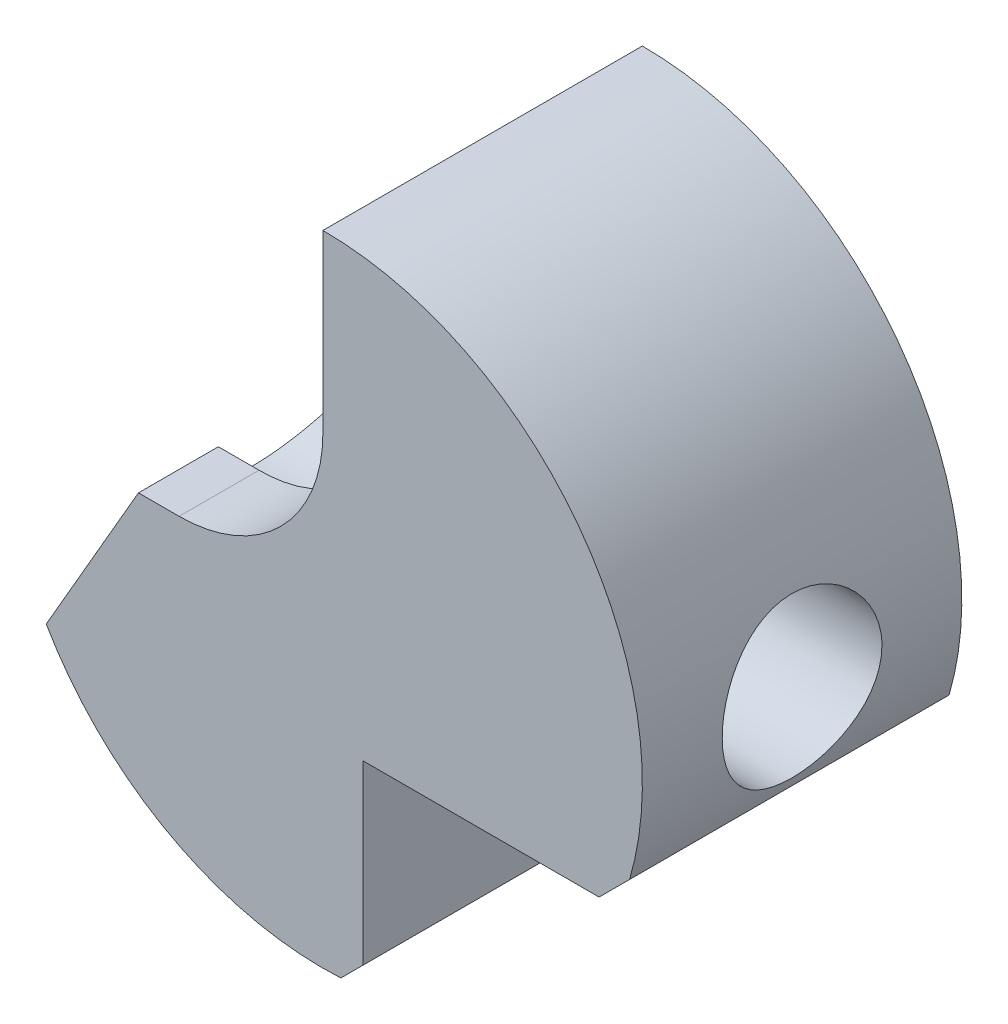
SolidWorks part; units mm, degrees
ref_plane "Front Plane" through (0, 0, 0) normal (0, 0, 1) x (1, 0, 0)
ref_plane "Top Plane" through (0, 0, 0) normal (0, 1, 0) x (1, 0, 0)
ref_plane "Right Plane" through (0, 0, 0) normal (1, 0, 0) x (0, 0, -1)
sketch "Sketch1" plane through (0, 0, 0) normal (0, 0, 1) x (1, 0, 0)
  circle A0 centre (0, 0) radius 20
  dimension "D1" = 40
extrude "Boss-Extrude1" add sketch "Sketch1" along normal mid plane 20
sketch "Sketch2" plane through (0, 0, 10) normal (0, 0, 1) x (1, 0, 0)
  line L0 (0, 20) -> (0, 24.3366)
  line L1 (0, 24.3366) -> (-29.8594, 24.3366)
  line L2 (-29.8594, 24.3366) -> (-29.8594, -31.718)
  line L3 (-29.8594, -31.718) -> (0, 20)
  circle A0 centre (0, 0) radius 20 construction
  dimension "D1" = 150
extrude "Cut-Extrude1" cut sketch "Sketch2" against normal mid plane 66
sketch "Sketch4" plane through (0, 0, 0) normal (1, 0, 0) x (0, 0, -1)
  line L1 (0, 0) -> (-24.3942, 0)
  line L2 (0, 0) -> (0, 23.6702)
  line L3 (0, 23.6702) -> (-24.3942, 23.6702)
  line L4 (-24.3942, 0) -> (-24.3942, 23.6702)
sketch "Sketch5" plane through (0, 0, 0) normal (0, 0, 1) x (1, 0, 0)
  line L1 (0, 0) -> (-27.4005, 0)
  line L2 (0, 0) -> (0, 25.3937)
  line L3 (0, 25.3937) -> (-27.4005, 25.3937)
  line L4 (-27.4005, 0) -> (-27.4005, 25.3937)
extrude "Cut-Extrude3" cut sketch "Sketch5" along normal blind 66
fillet "Fillet1" radius 9 1 edges at (0, 0, 5)
sketch "Sketch6" plane through (0, 0, 0) normal (0, 0, 1) x (1, 0, 0)
  line L1 (2.5, -7.5) -> (28.8031, -7.5)
  line L2 (2.5, -7.5) -> (2.5, -26.8651)
  line L3 (2.5, -26.8651) -> (28.8031, -26.8651)
  line L4 (28.8031, -7.5) -> (28.8031, -26.8651)
  dimension "D1" = 7.5
  dimension "D2" = 2.5
extrude "Cut-Extrude4" cut sketch "Sketch6" against normal mid plane 66
chamfer "Chamfer1" distance 1.25 angle 45 1 edges at (2.5, -19.8431, 0) first distance on face at (2.5, -13.6716, 0)
chamfer "Chamfer2" distance 1.25 angle 45 1 edges at (18.5405, -7.5, 0) first distance on face at (10.5202, -7.5, 0)
sketch "Sketch7" plane through (0, 0, 0) normal (1, 0, 0) x (0, 0, -1)
  circle A0 centre (0, 0) radius 5
extrude "Cut-Extrude5" cut sketch "Sketch7" against normal mid plane 66
